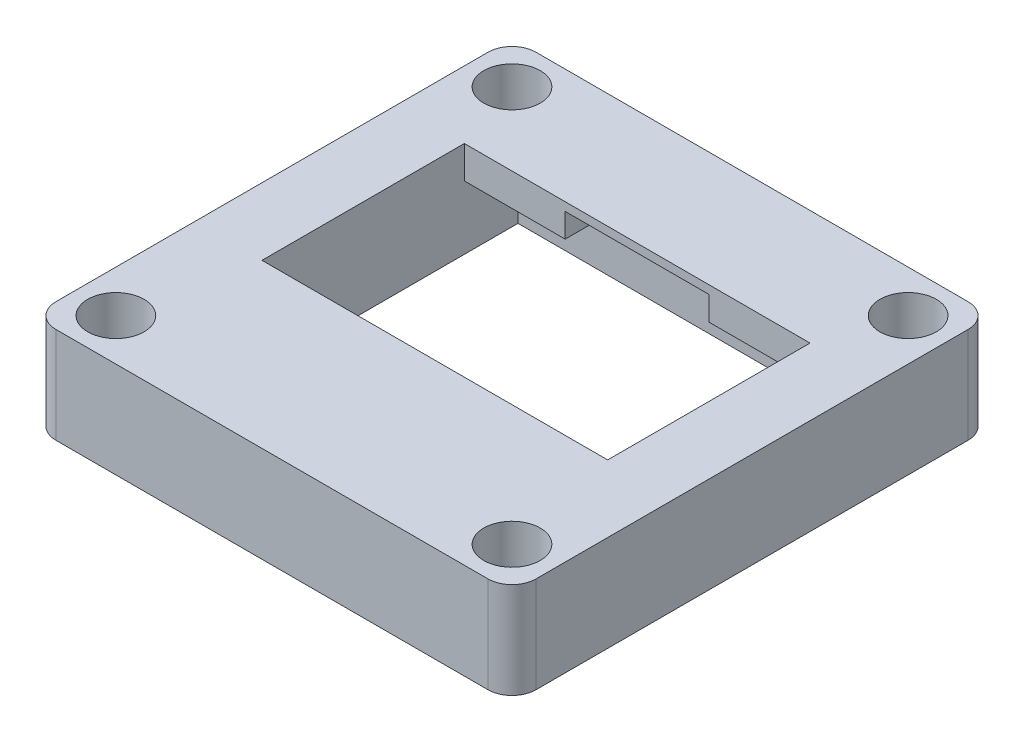
SolidWorks part; units mm, degrees
material "ABS"
ref_plane "Спереди" through (0, 0, 0) normal (0, 0, 1) x (1, 0, 0)
ref_plane "Сверху" through (0, 0, 0) normal (0, 1, 0) x (1, 0, 0)
ref_plane "Справа" through (0, 0, 0) normal (1, 0, 0) x (0, 0, -1)
sketch "габариты дисплея" plane through (0, 0, 0) normal (0, 1, 0) x (1, 0, 0)
  line L1 (-13.6, -13.6) -> (13.6, -13.6)
  line L2 (-13.6, -13.6) -> (-13.6, 13.6)
  line L3 (-13.6, 13.6) -> (13.6, 13.6)
  line L4 (13.6, -13.6) -> (13.6, 13.6)
  line L5 (-13.6, -13.6) -> (13.6, 13.6) construction
  line L6 (-13.6, 13.6) -> (13.6, -13.6) construction
  line L7 (-13.6, -9.63) -> (13.6, -9.63)
  line L8 (-13.6, -9.63) -> (-13.6, 9.63)
  line L9 (-13.6, 9.63) -> (13.6, 9.63)
  line L10 (13.6, -9.63) -> (13.6, 9.63)
  line L11 (-13.6, -9.63) -> (13.6, 9.63) construction
  line L12 (-13.6, 9.63) -> (13.6, -9.63) construction
  line L13 (-11.6, -11.6) -> (11.6, -11.6) construction
  line L14 (-11.6, -11.6) -> (-11.6, 11.6) construction
  line L15 (-11.6, 11.6) -> (11.6, 11.6) construction
  line L16 (11.6, -11.6) -> (11.6, 11.6) construction
  line L17 (-11.6, -11.6) -> (11.6, 11.6) construction
  line L18 (-11.6, 11.6) -> (11.6, -11.6) construction
  circle A0 centre (-11.6, 11.6) radius 1.25
  circle A1 centre (11.6, 11.6) radius 1.25
  circle A2 centre (11.6, -11.6) radius 1.25
  circle A3 centre (-11.6, -11.6) radius 1.25
  point P0 (0, 0)
  point P6 (0, 0)
  point P12 (0, 0)
  dimension "D5" = 2.5
  dimension "D1" = 19.26
  dimension "D2" = 27.2
  dimension "D3" = 27.2
  dimension "D4" = 2
sketch "Эскиз1" plane through (0, 0, 0) normal (0, 1, 0) x (1, 0, 0)
  line L1 (-20, 20) -> (20, 20)
  line L2 (-20, 20) -> (-20, -20)
  line L3 (-20, -20) -> (20, -20)
  line L4 (20, 20) -> (20, -20)
  line L5 (-20, 20) -> (20, -20) construction
  line L6 (-20, -20) -> (20, 20) construction
  point P0 (0, 0)
  dimension "D1" = 40
  dimension "D2" = 40
extrude "тело" add sketch "Эскиз1" along normal blind 8
sketch "Эскиз2" plane through (0, 0, 0) normal (0, -1, 0) x (1, 0, 0)
  line L0 (-13.6, 13.6) -> (13.6, 13.6) construction
  line L1 (-14.4, -14.9) -> (14.4, -14.9)
  line L2 (-14.4, -14.9) -> (-14.4, 14.9)
  line L3 (-14.4, 14.9) -> (14.4, 14.9)
  line L4 (14.4, -14.9) -> (14.4, 14.9)
  line L5 (-14.4, -14.9) -> (14.4, 14.9) construction
  line L6 (-14.4, 14.9) -> (14.4, -14.9) construction
  line L7 (13.6, 13.6) -> (13.6, -13.6) construction
  point P0 (0, 0)
  dimension "D1" = 1.3
  dimension "D2" = 0.8
extrude "углубление для платы" cut sketch "Эскиз2" against normal offset from surface (5.3 mm away) 2.7 up to face at (0, 8, 0)
sketch "Эскиз3" plane through (0, 5.3, 0) normal (0, -1, 0) x (1, 0, 0)
  line L0 (14.4, -14.9) -> (14.4, 14.9) construction
  line L1 (-14.4, -10.43) -> (14.4, -10.43)
  line L2 (-14.4, -10.43) -> (-14.4, 10.43)
  line L3 (-14.4, 10.43) -> (14.4, 10.43)
  line L4 (14.4, -10.43) -> (14.4, 10.43)
  line L5 (-14.4, -10.43) -> (14.4, 10.43) construction
  line L6 (-14.4, 10.43) -> (14.4, -10.43) construction
  line L7 (-13.6, 9.63) -> (13.6, 9.63) construction
  point P0 (0, 0)
  dimension "D1" = 0.8
extrude "отверстие для дисплея" cut sketch "Эскиз3" against normal through all
sketch "Эскиз4" plane through (0, 5.3, 0) normal (0, -1, 0) x (1, 0, 0)
  line L0 (14.4, 10.43) -> (-14.4, 10.43) construction
  line L1 (-6, 10.43) -> (6, 10.43)
  line L2 (-6, 10.43) -> (-6, 14.9)
  line L3 (-6, 14.9) -> (6, 14.9)
  line L4 (6, 10.43) -> (6, 14.9)
  line L5 (14.4, 14.9) -> (-14.4, 14.9) construction
  line L6 (-14.4, -10.43) -> (14.4, -10.43) construction
  line L7 (6, -10.43) -> (-6, -10.43)
  line L8 (6, -10.43) -> (6, -14.9)
  line L9 (6, -14.9) -> (-6, -14.9)
  line L10 (-6, -10.43) -> (-6, -14.9)
  line L11 (-14.4, -14.9) -> (14.4, -14.9) construction
  point P16 (0, -10.43)
  point P18 (0, 10.43)
  dimension "D1" = 12
extrude "углубление для шлейфа и пинов" cut sketch "Эскиз4" against normal offset from surface (2 mm away) 0.7 up to face at (0, 8, 0)
sketch "Эскиз5" plane through (0, 0, 10.43) normal (0, 0, -1) x (-1, 0, 0)
  line L1 (-14.4, 8) -> (-14.4, 5.3) construction
  line L2 (14.4, 8) -> (-14.4, 8)
  line L3 (14.4, 8) -> (14.4, 7.5)
  line L4 (14.4, 7.5) -> (-14.4, 7.5)
  line L6 (-14.4, 8) -> (-14.4, 7.5)
  dimension "D1" = 0.5
extrude "щит нижней части дисплея" add sketch "Эскиз5" along normal blind 4
sketch "Эскиз7" plane through (0, 0, 0) normal (0, -1, 0) x (1, 0, 0)
  line L1 (-16.5, -16.5) -> (16.5, -16.5) construction
  line L2 (-16.5, -16.5) -> (-16.5, 16.5) construction
  line L3 (-16.5, 16.5) -> (16.5, 16.5) construction
  line L4 (16.5, -16.5) -> (16.5, 16.5) construction
  line L5 (-16.5, -16.5) -> (16.5, 16.5) construction
  line L6 (-16.5, 16.5) -> (16.5, -16.5) construction
  circle A0 centre (-16.5, 16.5) radius 1.25
  circle A1 centre (16.5, 16.5) radius 1.25
  circle A2 centre (16.5, -16.5) radius 1.25
  circle A3 centre (-16.5, -16.5) radius 1.25
  point P0 (0, 0)
  dimension "D3" = 2.5
  dimension "D1" = 33
  dimension "D2" = 33
extrude "крепежные отверстия" cut sketch "Эскиз7" against normal through all
fillet "Скругление1" radius 2 4 edges at (-20, 4, -20) (20, 4, -20) (20, 4, 20) (-20, 4, 20)
sketch "Эскиз8" plane through (0, 8, 0) normal (0, 1, 0) x (1, 0, 0)
  circle A0 centre (-16.5, 16.5) radius 2.35
  circle A1 centre (-16.5, -16.5) radius 2.35
  circle A2 centre (16.5, -16.5) radius 2.35
  circle A3 centre (16.5, 16.5) radius 2.35
  dimension "D1" = 4.7
extrude "Углубления под шляпки" cut sketch "Эскиз8" against normal blind 4
